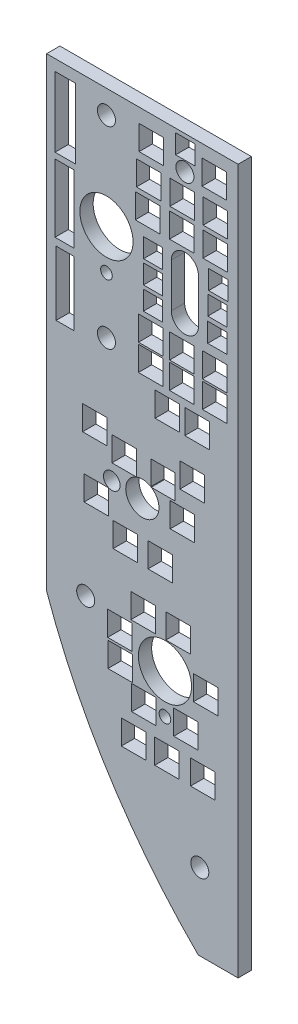
SolidWorks part; units mm, degrees
material "Acrylic (Medium-high impact)"
ref_plane "Front Plane" through (0, 0, 0) normal (0, 0, 1) x (1, 0, 0)
ref_plane "Top Plane" through (0, 0, 0) normal (0, 1, 0) x (1, 0, 0)
ref_plane "Right Plane" through (0, 0, 0) normal (1, 0, 0) x (0, 0, -1)
sketch "Sketch1" plane through (0, 0, 0) normal (0, 0, 1) x (1, 0, 0)
  line L4 (-45.72, 26.9875) -> (-45.72, -84.1375)
  line L5 (-9.525, -141.2875) -> (0, -141.2875)
  line L6 (0, -141.2875) -> (0, 26.9875)
  line L7 (0, 26.9875) -> (-45.72, 26.9875)
  line L8 (-45.72, 26.9875) -> (-45.72, -84.1375)
  line L9 (-9.525, -141.2875) -> (0, -141.2875)
  line L10 (0, -141.2875) -> (0, 26.9875)
  line L11 (0, 26.9875) -> (-45.72, 26.9875)
  arc A1 (-45.72, -84.1375) -> (-9.525, -141.2875) centre (97.9169, -33.2042) ccw
  arc A2 (-45.72, -84.1375) -> (-9.525, -141.2875) centre (97.9169, -33.2042) ccw
  dimension "D1" = 0
extrude "Boss-Extrude1" add sketch "Sketch1" against normal blind 3.175
hole_wizard "1/2 (0.5) Diameter Hole1" positions "Sketch4" profile "Sketch3" hole size "1/2" standard "ANSI Inch" end condition through all
sketch "Sketch4" plane through (0, 0, 0) normal (0, 0, 1) x (1, 0, 0)
  point P0 (-17.4625, -86.5505)
  point P4 (-31.4325, -1.6203)
sketch "Sketch3" plane through (-17.4625, -86.5505, 0) normal (1, 0, 0) x (0, -1, 0)
  line L0 (0, 0) -> (0, 3.175)
  line L1 (0, 3.175) -> (6.35, 3.175)
  line L2 (6.35, 3.175) -> (6.35, 0)
  line L5 (6.35, 0) -> (0, 0)
  line L11 (0, -6.35) -> (0, 107.95) construction
  dimension "Thru Hole Dia." = 12.7
  dimension "Thru Hole Depth" = 3.175
hole_wizard "5/16 (0.3125) Diameter Hole1" positions "Sketch6" profile "Sketch5" hole size "5/16" standard "ANSI Inch" end condition through all
sketch "Sketch6" plane through (0, 0, 0) normal (0, 0, 1) x (1, 0, 0)
  point P0 (-22.86, -53.5305)
sketch "Sketch5" plane through (-22.86, -53.5305, 0) normal (1, 0, 0) x (0, -1, 0)
  line L0 (0, 0) -> (0, 3.175)
  line L1 (0, 3.175) -> (3.9687, 3.175)
  line L2 (3.9687, 3.175) -> (3.9687, 0)
  line L5 (3.9687, 0) -> (0, 0)
  line L11 (0, -6.35) -> (0, 107.95) construction
  dimension "Thru Hole Dia." = 7.9375
  dimension "Thru Hole Depth" = 3.175
hole_wizard "5/32 (0.15625) Diameter Hole1" positions "Sketch8" profile "Sketch7" hole size "5/32" standard "ANSI Inch" end condition through all
sketch "Sketch8" plane through (0, 0, 0) normal (0, 0, 1) x (1, 0, 0)
  line L0 (-22.86, -49.5617) -> (-22.86, -53.5305) construction
  circle A0 centre (-22.86, -53.5305) radius 3.9688 construction
  point P11 (-30.1611, -53.5305)
sketch "Sketch7" plane through (-30.1611, -53.5305, 0) normal (1, 0, 0) x (0, -1, 0)
  line L0 (0, 0) -> (0, 3.175)
  line L1 (0, 3.175) -> (1.9844, 3.175)
  line L2 (1.9844, 3.175) -> (1.9844, 0)
  line L5 (1.9844, 0) -> (0, 0)
  line L11 (0, -6.35) -> (0, 107.95) construction
  dimension "Thru Hole Dia." = 3.9688
  dimension "Thru Hole Depth" = 3.175
hole_wizard "7/64 (0.10938) Diameter Hole1" positions "Sketch10" profile "Sketch9" hole size "7/64" standard "ANSI Inch" end condition through all
sketch "Sketch10" plane through (0, 0, 0) normal (0, 0, 1) x (1, 0, 0)
  point P0 (-17.4646, -95.9667)
  point P3 (-31.4325, -11.1589)
sketch "Sketch9" plane through (-17.4646, -95.9667, 0) normal (1, 0, 0) x (0, -1, 0)
  line L0 (0, 0) -> (0, 3.175)
  line L1 (0, 3.175) -> (1.3891, 3.175)
  line L2 (1.3891, 3.175) -> (1.3891, 0)
  line L5 (1.3891, 0) -> (0, 0)
  line L11 (0, -6.35) -> (0, 107.95) construction
  dimension "Thru Hole Dia." = 2.7783
  dimension "Thru Hole Depth" = 3.175
sketch "Sketch11" plane through (0, 0, -3.175) normal (0, 0, -1) x (-1, 0, 0)
  line L5 (19.8437, -15.24) -> (19.8437, 3.175)
  line L6 (19.8437, 3.175) -> (8.7312, 3.175)
  line L7 (8.7312, 3.175) -> (8.7312, -15.24)
  line L8 (8.7312, -15.24) -> (19.8437, -15.24)
  line L9 (19.8437, -15.24) -> (19.8437, 3.175)
  line L10 (19.8437, 3.175) -> (8.7312, 3.175)
  line L11 (8.7312, 3.175) -> (8.7312, -15.24)
  line L12 (8.7312, -15.24) -> (19.8437, -15.24)
  dimension "D1" = 0
extrude "Cut-Extrude4" [suppressed] cut sketch "Sketch11" against normal through all
hole_wizard "#6 Clearance Hole1" positions "Sketch13" profile "Sketch12" hole size "#6" standard "ANSI Inch" end condition through all
sketch "Sketch13" plane through (0, 0, -3.175) normal (0, 0, -1) x (-1, 0, 0)
  point P0 (12.7, 19.05)
  point P3 (36.3855, -80.4545)
  point P6 (9.144, -122.9995)
  point P10 (31.4325, -24.62)
  point P13 (31.4325, 21.4048)
sketch "Sketch12" plane through (-12.7, 19.05, -3.175) normal (1, 0, 0) x (0, 1, 0)
  line L0 (0, 0) -> (0, 3.175)
  line L1 (0, 3.175) -> (2.1526, 3.175)
  line L2 (2.1526, 3.175) -> (2.1526, 0)
  line L5 (2.1526, 0) -> (0, 0)
  line L11 (0, -6.35) -> (0, 107.95) construction
  dimension "Thru Hole Dia." = 4.3053
  dimension "Thru Hole Depth" = 3.175
hole_wizard "#16 (0.177) Diameter Hole1" positions "Sketch15" profile "Sketch14" hole size "#16" standard "ANSI Inch" end condition through all
sketch "Sketch15" plane through (0, 0, -3.175) normal (0, 0, -1) x (-1, 0, 0)
  line L5 (12.7, 2.794) -> (12.7, -14.859) construction
  line L6 (12.7, -6.0325) -> (17.8753, -6.0325) construction
  point P26 (12.7, -0.7804)
  point P33 (12.7, -11.2846)
sketch "Sketch14" plane through (-12.7, -0.7804, -3.175) normal (1, 0, 0) x (0, 1, 0)
  line L0 (0, 0) -> (0, 3.175)
  line L1 (0, 3.175) -> (2.2479, 3.175)
  line L2 (2.2479, 3.175) -> (2.2479, 0)
  line L5 (2.2479, 0) -> (0, 0)
  line L11 (0, -6.35) -> (0, 107.95) construction
  dimension "Thru Hole Dia." = 4.4958
  dimension "Thru Hole Depth" = 3.175
sketch "Sketch16" plane through (0, 0, -4.775) normal (0, 0, -1) x (-1, 0, 0)
  line L0 (12.7, -11.2846) -> (12.7, -0.7804) construction
  line L1 (2.6659, -22.1354) -> (8.5079, -22.1354)
  line L2 (2.6659, -22.1354) -> (2.6659, -27.9774)
  line L3 (2.6659, -27.9774) -> (8.5079, -27.9774)
  line L4 (8.5079, -22.1354) -> (8.5079, -27.9774)
  line L5 (2.6659, -22.1354) -> (8.5079, -27.9774) construction
  line L6 (2.6659, -27.9774) -> (8.5079, -22.1354) construction
  line L7 (10.5519, -22.1354) -> (16.3939, -22.1354)
  line L8 (10.5519, -22.1354) -> (10.5519, -27.9774)
  line L9 (10.5519, -27.9774) -> (16.3939, -27.9774)
  line L10 (16.3939, -22.1354) -> (16.3939, -27.9774)
  line L11 (10.5519, -22.1354) -> (16.3939, -27.9774) construction
  line L12 (10.5519, -27.9774) -> (16.3939, -22.1354) construction
  line L13 (17.9569, -22.1354) -> (23.7989, -22.1354)
  line L14 (17.9569, -22.1354) -> (17.9569, -27.9774)
  line L15 (17.9569, -27.9774) -> (23.7989, -27.9774)
  line L16 (23.7989, -22.1354) -> (23.7989, -27.9774)
  line L17 (17.9569, -22.1354) -> (23.7989, -27.9774) construction
  line L18 (17.9569, -27.9774) -> (23.7989, -22.1354) construction
  line L19 (17.9319, -15.8614) -> (23.7739, -15.8614)
  line L20 (17.9319, -15.8614) -> (17.9319, -21.7034)
  line L21 (17.9319, -21.7034) -> (23.7739, -21.7034)
  line L22 (23.7739, -15.8614) -> (23.7739, -21.7034)
  line L23 (17.9319, -15.8614) -> (23.7739, -21.7034) construction
  line L24 (17.9319, -21.7034) -> (23.7739, -15.8614) construction
  line L25 (10.5149, -15.8364) -> (16.3569, -15.8364)
  line L26 (10.5149, -15.8364) -> (10.5149, -21.6784)
  line L27 (10.5149, -21.6784) -> (16.3569, -21.6784)
  line L28 (16.3569, -15.8364) -> (16.3569, -21.6784)
  line L29 (10.5149, -15.8364) -> (16.3569, -21.6784) construction
  line L30 (10.5149, -21.6784) -> (16.3569, -15.8364) construction
  line L31 (2.6919, -15.8114) -> (8.5339, -15.8114)
  line L32 (2.6919, -15.8114) -> (2.6919, -21.6534)
  line L33 (2.6919, -21.6534) -> (8.5339, -21.6534)
  line L34 (8.5339, -15.8114) -> (8.5339, -21.6534)
  line L35 (2.6919, -15.8114) -> (8.5339, -21.6534) construction
  line L36 (2.6919, -21.6534) -> (8.5339, -15.8114) construction
  line L41 (39.2165, -27.0307) -> (43.4505, -27.0307)
  line L42 (39.2165, -27.0307) -> (39.2165, -11.6644)
  line L47 (39.2165, -11.6644) -> (43.4505, -11.6644)
  line L48 (43.4505, -27.0307) -> (43.4505, -11.6644)
  line L53 (39.2165, 6.231) -> (43.7187, 6.231)
  line L54 (39.2165, 6.231) -> (39.2165, -9.9754)
  line L55 (39.2165, -9.9754) -> (43.7187, -9.9754)
  line L56 (43.7187, 6.231) -> (43.7187, -9.9754)
  line L57 (38.8582, 7.6135) -> (43.7187, 7.6135)
  line L58 (38.8582, 7.6135) -> (38.8582, 24.3196)
  line L59 (38.8582, 24.3196) -> (43.7187, 24.3196)
  line L60 (43.7187, 7.6135) -> (43.7187, 24.3196)
  line L61 (12.7249, -29.6544) -> (6.8829, -29.6544)
  line L62 (12.7249, -29.6544) -> (12.7249, -35.4964)
  line L63 (12.7249, -35.4964) -> (6.8829, -35.4964)
  line L64 (6.8829, -29.6544) -> (6.8829, -35.4964)
  line L65 (12.7249, -29.6544) -> (6.8829, -35.4964) construction
  line L66 (12.7249, -35.4964) -> (6.8829, -29.6544) construction
  line L67 (19.8109, -29.6034) -> (13.9689, -29.6034)
  line L68 (19.8109, -29.6034) -> (19.8109, -35.4454)
  line L69 (19.8109, -35.4454) -> (13.9689, -35.4454)
  line L70 (13.9689, -29.6034) -> (13.9689, -35.4454)
  line L71 (19.8109, -29.6034) -> (13.9689, -35.4454) construction
  line L72 (19.8109, -35.4454) -> (13.9689, -29.6034) construction
  line L73 (5.5089, -101.4346) -> (11.3509, -101.4346)
  line L74 (5.5089, -101.4346) -> (5.5089, -107.2766)
  line L75 (5.5089, -107.2766) -> (11.3509, -107.2766)
  line L76 (11.3509, -101.4346) -> (11.3509, -107.2766)
  line L77 (5.5089, -101.4346) -> (11.3509, -107.2766) construction
  line L78 (5.5089, -107.2766) -> (11.3509, -101.4346) construction
  line L79 (14.0689, -101.4088) -> (19.9109, -101.4088)
  line L80 (14.0689, -101.4088) -> (14.0689, -107.2508)
  line L81 (14.0689, -107.2508) -> (19.9109, -107.2508)
  line L82 (19.9109, -101.4088) -> (19.9109, -107.2508)
  line L83 (14.0689, -101.4088) -> (19.9109, -107.2508) construction
  line L84 (14.0689, -107.2508) -> (19.9109, -101.4088) construction
  line L85 (22.0469, -101.4342) -> (27.8889, -101.4342)
  line L86 (22.0469, -101.4342) -> (22.0469, -107.2762)
  line L87 (22.0469, -107.2762) -> (27.8889, -107.2762)
  line L88 (27.8889, -101.4342) -> (27.8889, -107.2762)
  line L89 (22.0469, -101.4342) -> (27.8889, -107.2762) construction
  line L90 (22.0469, -107.2762) -> (27.8889, -101.4342) construction
  line L91 (9.5239, -93.1288) -> (15.3659, -93.1288)
  line L92 (9.5239, -93.1288) -> (9.5239, -98.9708)
  line L93 (9.5239, -98.9708) -> (15.3659, -98.9708)
  line L94 (15.3659, -93.1288) -> (15.3659, -98.9708)
  line L95 (9.5239, -93.1288) -> (15.3659, -98.9708) construction
  line L96 (9.5239, -98.9708) -> (15.3659, -93.1288) construction
  line L97 (19.5569, -93.0776) -> (25.3989, -93.0776)
  line L98 (19.5569, -93.0776) -> (19.5569, -98.9196)
  line L99 (19.5569, -98.9196) -> (25.3989, -98.9196)
  line L100 (25.3989, -93.0776) -> (25.3989, -98.9196)
  line L101 (19.5569, -93.0776) -> (25.3989, -98.9196) construction
  line L102 (19.5569, -98.9196) -> (25.3989, -93.0776) construction
  line L103 (4.8249, -83.6546) -> (10.6669, -83.6546)
  line L104 (4.8249, -83.6546) -> (4.8249, -89.4966)
  line L105 (4.8249, -89.4966) -> (10.6669, -89.4966)
  line L106 (10.6669, -83.6546) -> (10.6669, -89.4966)
  line L107 (4.8249, -83.6546) -> (10.6669, -89.4966) construction
  line L108 (4.8249, -89.4966) -> (10.6669, -83.6546) construction
  line L109 (25.2329, -86.9818) -> (31.0749, -86.9818)
  line L110 (25.2329, -86.9818) -> (25.2329, -92.8238)
  line L111 (25.2329, -92.8238) -> (31.0749, -92.8238)
  line L112 (31.0749, -86.9818) -> (31.0749, -92.8238)
  line L113 (25.2329, -86.9818) -> (31.0749, -92.8238) construction
  line L114 (25.2329, -92.8238) -> (31.0749, -86.9818) construction
  line L115 (25.2959, -80.5808) -> (31.1379, -80.5808)
  line L116 (25.2959, -80.5808) -> (25.2959, -86.4228)
  line L117 (25.2959, -86.4228) -> (31.1379, -86.4228)
  line L118 (31.1379, -80.5808) -> (31.1379, -86.4228)
  line L119 (25.2959, -80.5808) -> (31.1379, -86.4228) construction
  line L120 (25.2959, -86.4228) -> (31.1379, -80.5808) construction
  line L121 (19.7609, -74.1546) -> (25.6029, -74.1546)
  line L122 (19.7609, -74.1546) -> (19.7609, -79.9966)
  line L123 (19.7609, -79.9966) -> (25.6029, -79.9966)
  line L124 (25.6029, -74.1546) -> (25.6029, -79.9966)
  line L125 (19.7609, -74.1546) -> (25.6029, -79.9966) construction
  line L126 (19.7609, -79.9966) -> (25.6029, -74.1546) construction
  line L127 (11.4019, -74.1804) -> (17.2439, -74.1804)
  line L128 (11.4019, -74.1804) -> (11.4019, -80.0224)
  line L129 (11.4019, -80.0224) -> (17.2439, -80.0224)
  line L130 (17.2439, -74.1804) -> (17.2439, -80.0224)
  line L131 (11.4019, -74.1804) -> (17.2439, -80.0224) construction
  line L132 (11.4019, -80.0224) -> (17.2439, -74.1804) construction
  line L133 (15.6709, -61.6074) -> (21.5129, -61.6074)
  line L134 (15.6709, -61.6074) -> (15.6709, -67.4494)
  line L135 (15.6709, -67.4494) -> (21.5129, -67.4494)
  line L136 (21.5129, -61.6074) -> (21.5129, -67.4494)
  line L137 (15.6709, -61.6074) -> (21.5129, -67.4494) construction
  line L138 (15.6709, -67.4494) -> (21.5129, -61.6074) construction
  line L139 (24.0019, -61.582) -> (29.8439, -61.582)
  line L140 (24.0019, -61.582) -> (24.0019, -67.424)
  line L141 (24.0019, -67.424) -> (29.8439, -67.424)
  line L142 (29.8439, -61.582) -> (29.8439, -67.424)
  line L143 (24.0019, -61.582) -> (29.8439, -67.424) construction
  line L144 (24.0019, -67.424) -> (29.8439, -61.582) construction
  line L145 (30.9369, -55.4098) -> (36.7789, -55.4098)
  line L146 (30.9369, -55.4098) -> (30.9369, -61.2518)
  line L147 (30.9369, -61.2518) -> (36.7789, -61.2518)
  line L148 (36.7789, -55.4098) -> (36.7789, -61.2518)
  line L149 (30.9369, -55.4098) -> (36.7789, -61.2518) construction
  line L150 (30.9369, -61.2518) -> (36.7789, -55.4098) construction
  line L151 (10.3599, -50.66) -> (16.2019, -50.66)
  line L152 (10.3599, -50.66) -> (10.3599, -56.502)
  line L153 (10.3599, -56.502) -> (16.2019, -56.502)
  line L154 (16.2019, -50.66) -> (16.2019, -56.502)
  line L155 (10.3599, -50.66) -> (16.2019, -56.502) construction
  line L156 (10.3599, -56.502) -> (16.2019, -50.66) construction
  line L157 (8.0509, -41.2874) -> (13.8929, -41.2874)
  line L158 (8.0509, -41.2874) -> (8.0509, -47.1294)
  line L159 (8.0509, -47.1294) -> (13.8929, -47.1294)
  line L160 (13.8929, -41.2874) -> (13.8929, -47.1294)
  line L161 (8.0509, -41.2874) -> (13.8929, -47.1294) construction
  line L162 (8.0509, -47.1294) -> (13.8929, -41.2874) construction
  line L163 (15.0109, -44.3354) -> (20.8529, -44.3354)
  line L164 (15.0109, -44.3354) -> (15.0109, -50.1774)
  line L165 (15.0109, -50.1774) -> (20.8529, -50.1774)
  line L166 (20.8529, -44.3354) -> (20.8529, -50.1774)
  line L167 (15.0109, -44.3354) -> (20.8529, -50.1774) construction
  line L168 (15.0109, -50.1774) -> (20.8529, -44.3354) construction
  line L169 (24.2819, -43.9798) -> (30.1239, -43.9798)
  line L170 (24.2819, -43.9798) -> (24.2819, -49.8218)
  line L171 (24.2819, -49.8218) -> (30.1239, -49.8218)
  line L172 (30.1239, -43.9798) -> (30.1239, -49.8218)
  line L173 (24.2819, -43.9798) -> (30.1239, -49.8218) construction
  line L174 (24.2819, -49.8218) -> (30.1239, -43.9798) construction
  line L175 (31.2919, -41.0588) -> (37.1339, -41.0588)
  line L176 (31.2919, -41.0588) -> (31.2919, -46.9008)
  line L177 (31.2919, -46.9008) -> (37.1339, -46.9008)
  line L178 (37.1339, -41.0588) -> (37.1339, -46.9008)
  line L179 (31.2919, -41.0588) -> (37.1339, -46.9008) construction
  line L180 (31.2919, -46.9008) -> (37.1339, -41.0588) construction
  line L185 (9.4609, -11.2846) -> (9.4609, -0.7804)
  line L186 (15.9391, -11.2846) -> (15.9391, -0.7804)
  line L193 (2.6809, -9.0944) -> (7.2529, -9.0944)
  line L194 (2.6809, -9.0944) -> (2.6809, -13.6664)
  line L195 (2.6809, -13.6664) -> (7.2529, -13.6664)
  line L196 (7.2529, -9.0944) -> (7.2529, -13.6664)
  line L197 (2.6809, -9.0944) -> (7.2529, -13.6664) construction
  line L198 (2.6809, -13.6664) -> (7.2529, -9.0944) construction
  line L199 (2.6659, -3.4664) -> (7.2379, -3.4664)
  line L200 (2.6659, -3.4664) -> (2.6659, -8.0384)
  line L201 (2.6659, -8.0384) -> (7.2379, -8.0384)
  line L202 (7.2379, -3.4664) -> (7.2379, -8.0384)
  line L203 (2.6659, -3.4664) -> (7.2379, -8.0384) construction
  line L204 (2.6659, -8.0384) -> (7.2379, -3.4664) construction
  line L205 (2.4609, 1.9176) -> (7.0329, 1.9176)
  line L206 (2.4609, 1.9176) -> (2.4609, -2.6544)
  line L207 (2.4609, -2.6544) -> (7.0329, -2.6544)
  line L208 (7.0329, 1.9176) -> (7.0329, -2.6544)
  line L209 (2.4609, 1.9176) -> (7.0329, -2.6544) construction
  line L210 (2.4609, -2.6544) -> (7.0329, 1.9176) construction
  line L211 (2.5389, 9.2076) -> (8.3809, 9.2076)
  line L212 (2.5389, 9.2076) -> (2.5389, 3.3656)
  line L213 (2.5389, 3.3656) -> (8.3809, 3.3656)
  line L214 (8.3809, 9.2076) -> (8.3809, 3.3656)
  line L215 (2.5389, 9.2076) -> (8.3809, 3.3656) construction
  line L216 (2.5389, 3.3656) -> (8.3809, 9.2076) construction
  line L217 (10.5379, 9.1566) -> (16.3799, 9.1566)
  line L218 (10.5379, 9.1566) -> (10.5379, 3.3146)
  line L219 (10.5379, 3.3146) -> (16.3799, 3.3146)
  line L220 (16.3799, 9.1566) -> (16.3799, 3.3146)
  line L221 (10.5379, 9.1566) -> (16.3799, 3.3146) construction
  line L222 (10.5379, 3.3146) -> (16.3799, 9.1566) construction
  line L223 (18.7049, 9.0556) -> (24.5469, 9.0556)
  line L224 (18.7049, 9.0556) -> (18.7049, 3.2136)
  line L225 (18.7049, 3.2136) -> (24.5469, 3.2136)
  line L226 (24.5469, 9.0556) -> (24.5469, 3.2136)
  line L227 (18.7049, 9.0556) -> (24.5469, 3.2136) construction
  line L228 (18.7049, 3.2136) -> (24.5469, 9.0556) construction
  line L229 (17.9969, 0.7356) -> (22.5689, 0.7356)
  line L230 (17.9969, 0.7356) -> (17.9969, -3.8364)
  line L231 (17.9969, -3.8364) -> (22.5689, -3.8364)
  line L232 (22.5689, 0.7356) -> (22.5689, -3.8364)
  line L233 (17.9969, 0.7356) -> (22.5689, -3.8364) construction
  line L234 (17.9969, -3.8364) -> (22.5689, 0.7356) construction
  line L235 (18.0219, -4.6994) -> (22.5939, -4.6994)
  line L236 (18.0219, -4.6994) -> (18.0219, -9.2714)
  line L237 (18.0219, -9.2714) -> (22.5939, -9.2714)
  line L238 (22.5939, -4.6994) -> (22.5939, -9.2714)
  line L239 (18.0219, -4.6994) -> (22.5939, -9.2714) construction
  line L240 (18.0219, -9.2714) -> (22.5939, -4.6994) construction
  line L241 (18.0479, -10.1354) -> (22.6199, -10.1354)
  line L242 (18.0479, -10.1354) -> (18.0479, -14.7074)
  line L243 (18.0479, -14.7074) -> (22.6199, -14.7074)
  line L244 (22.6199, -10.1354) -> (22.6199, -14.7074)
  line L245 (18.0479, -10.1354) -> (22.6199, -14.7074) construction
  line L246 (18.0479, -14.7074) -> (22.6199, -10.1354) construction
  line L247 (2.4859, 16.0666) -> (8.3279, 16.0666)
  line L248 (2.4859, 16.0666) -> (2.4859, 10.2246)
  line L249 (2.4859, 10.2246) -> (8.3279, 10.2246)
  line L250 (8.3279, 16.0666) -> (8.3279, 10.2246)
  line L251 (2.4859, 16.0666) -> (8.3279, 10.2246) construction
  line L252 (2.4859, 10.2246) -> (8.3279, 16.0666) construction
  line L253 (10.4389, 15.9896) -> (16.2809, 15.9896)
  line L254 (10.4389, 15.9896) -> (10.4389, 10.1476)
  line L255 (10.4389, 10.1476) -> (16.2809, 10.1476)
  line L256 (16.2809, 15.9896) -> (16.2809, 10.1476)
  line L257 (10.4389, 15.9896) -> (16.2809, 10.1476) construction
  line L258 (10.4389, 10.1476) -> (16.2809, 15.9896) construction
  line L259 (18.4399, 15.9896) -> (24.2819, 15.9896)
  line L260 (18.4399, 15.9896) -> (18.4399, 10.1476)
  line L261 (18.4399, 10.1476) -> (24.2819, 10.1476)
  line L262 (24.2819, 15.9896) -> (24.2819, 10.1476)
  line L263 (18.4399, 15.9896) -> (24.2819, 10.1476) construction
  line L264 (18.4399, 10.1476) -> (24.2819, 15.9896) construction
  line L265 (17.8049, 23.6096) -> (23.6469, 23.6096)
  line L266 (17.8049, 23.6096) -> (17.8049, 17.7676)
  line L267 (17.8049, 17.7676) -> (23.6469, 17.7676)
  line L268 (23.6469, 23.6096) -> (23.6469, 17.7676)
  line L269 (17.8049, 23.6096) -> (23.6469, 17.7676) construction
  line L270 (17.8049, 17.7676) -> (23.6469, 23.6096) construction
  line L271 (2.7659, 23.9906) -> (8.6079, 23.9906)
  line L272 (2.7659, 23.9906) -> (2.7659, 18.1486)
  line L273 (2.7659, 18.1486) -> (8.6079, 18.1486)
  line L274 (8.6079, 23.9906) -> (8.6079, 18.1486)
  line L275 (2.7659, 23.9906) -> (8.6079, 18.1486) construction
  line L276 (2.7659, 18.1486) -> (8.6079, 23.9906) construction
  line L277 (10.3369, 26.0476) -> (14.9089, 26.0476)
  line L278 (10.3369, 26.0476) -> (10.3369, 21.4756)
  line L279 (10.3369, 21.4756) -> (14.9089, 21.4756)
  line L280 (14.9089, 26.0476) -> (14.9089, 21.4756)
  line L281 (10.3369, 26.0476) -> (14.9089, 21.4756) construction
  line L282 (10.3369, 21.4756) -> (14.9089, 26.0476) construction
  arc A0 (9.4609, -11.2846) -> (15.9391, -11.2846) centre (12.7, -11.2846) ccw
  arc A1 (15.9391, -0.7804) -> (9.4609, -0.7804) centre (12.7, -0.7804) ccw
  point P0 (5.5869, -25.0564)
  point P6 (13.4729, -25.0564)
  point P12 (20.8779, -25.0564)
  point P18 (20.8529, -18.7824)
  point P24 (13.4359, -18.7574)
  point P30 (5.6129, -18.7324)
  point P50 (9.8039, -32.5754)
  point P57 (16.8899, -32.5244)
  point P63 (8.4299, -104.3556)
  point P69 (16.9899, -104.3298)
  point P75 (24.9679, -104.3552)
  point P81 (12.4449, -96.0498)
  point P87 (22.4779, -95.9986)
  point P93 (7.7459, -86.5756)
  point P99 (28.1539, -89.9028)
  point P105 (28.2169, -83.5018)
  point P111 (22.6819, -77.0756)
  point P117 (14.3229, -77.1014)
  point P123 (18.5919, -64.5284)
  point P129 (26.9229, -64.503)
  point P135 (33.8579, -58.3308)
  point P141 (13.2809, -53.581)
  point P147 (10.9719, -44.2084)
  point P153 (17.9319, -47.2564)
  point P159 (27.2029, -46.9008)
  point P165 (34.2129, -43.9798)
  point P173 (12.7, -6.0325)
  point P183 (4.9669, -11.3804)
  point P189 (4.9519, -5.7524)
  point P195 (4.7469, -0.3684)
  point P201 (5.4599, 6.2866)
  point P207 (13.4589, 6.2356)
  point P213 (21.6259, 6.1346)
  point P219 (20.2829, -1.5504)
  point P225 (20.3079, -6.9854)
  point P231 (20.3339, -12.4214)
  point P237 (5.4069, 13.1456)
  point P243 (13.3599, 13.0686)
  point P249 (21.3609, 13.0686)
  point P255 (20.7259, 20.6886)
  point P261 (5.6869, 21.0696)
  point P267 (12.6229, 23.7616)
  dimension "D1" = 5.842
  dimension "D2" = 5.842
  dimension "D3" = 4.572
extrude "Cut-Extrude5" cut sketch "Sketch16" against normal through all
